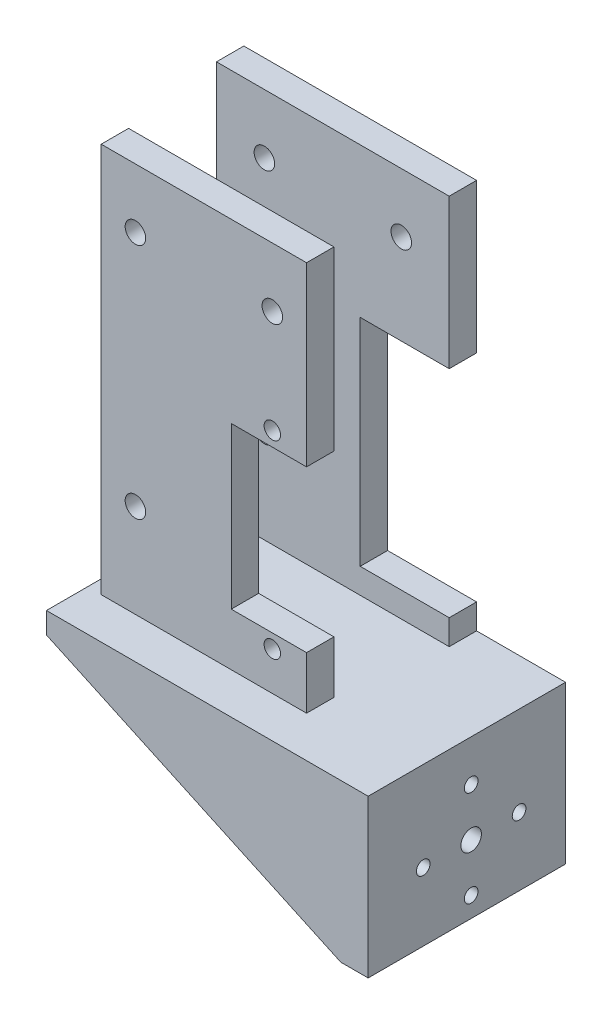
SolidWorks part; units mm, degrees
ref_plane "前视基准面" through (0, 0, 0) normal (0, 0, 1) x (1, 0, 0)
ref_plane "上视基准面" through (0, 0, 0) normal (0, 1, 0) x (1, 0, 0)
ref_plane "右视基准面" through (0, 0, 0) normal (1, 0, 0) x (0, 0, -1)
ref_plane "基准面1" through (30, 0, 0) normal (1, 0, 0) x (0, 0, -1)
sketch "草图1" plane through (0, 0, 0) normal (0, 0, 1) x (1, 0, 0)
  line L0 (0, 19.2229) -> (0, -22.2141) construction
  line L1 (-15, -26) -> (-15, -54)
  line L2 (-15, 26) -> (15, 26)
  line L3 (-15, 26) -> (-15, -26)
  line L6 (-15, 26) -> (15, -26) construction
  line L7 (-15, -26) -> (15, 26) construction
  line L8 (-15, -54) -> (30, -54)
  line L11 (15, 26) -> (15, 0.1667)
  line L12 (15, 0.1667) -> (4, 0.1667)
  line L13 (4, 0.1667) -> (4, -23.3333)
  line L14 (4, -23.3333) -> (15, -23.3333)
  line L15 (15, -23.3333) -> (15, -26)
  line L16 (15, -26) -> (15, -31)
  line L17 (15, -31) -> (30, -31)
  line L18 (30, -31) -> (30, -54)
  circle A0 centre (-10, 17.3333) radius 1.5
  circle A1 centre (10, 17.3333) radius 1.5
  circle A2 centre (-10, -17.3333) radius 1.5
  circle A4 centre (10, 2.2917) radius 1.2
  circle A5 centre (10, -25.3783) radius 1.2
  point P3 (0, 0)
  dimension "D6" = 3
  dimension "D7" = 3
  dimension "D8" = 3
  dimension "D14" = 2.4
  dimension "D15" = 2.4
  dimension "D16" = 6
  dimension "D1" = 30
  dimension "D2" = 52
  dimension "D3" = 10
  dimension "D4" = 10
  dimension "D5" = 10
  dimension "D9" = 28
  dimension "D10" = 45
  dimension "D11" = 17.5
  dimension "D12" = 19.625
  dimension "D13" = 8.045
  dimension "D17" = 10
  dimension "D18" = 10
  dimension "D19" = 6
  dimension "5" = 5
  dimension "D21" = 15
extrude "凸台-拉伸1" add sketch "草图1" along normal blind 4
sketch "草图2" plane through (30, 0, 0) normal (1, 0, 0) x (0, 0, -1)
  line L0 (-4.8995, -34.1005) -> (15, -34.1005)
  line L1 (15, -34.1005) -> (15, -54)
  line L2 (15, -54) -> (-4.8995, -54)
  line L7 (-4, -54) -> (0, -54) construction
  line L8 (-4.8995, -34.1005) -> (-4.8995, -54)
  circle A4 centre (0.1005, -39.1005) radius 1.5
  circle A5 centre (10, -39.1005) radius 1.5
  circle A6 centre (0.1005, -49) radius 1.5
  circle A7 centre (10, -49) radius 1.5
  dimension "D3" = 14
  dimension "D5" = 5
  dimension "D7" = 3
  dimension "D9" = 3
  dimension "D6" = 3
  dimension "D8" = 3
  dimension "D11" = 9.8995
  dimension "D2" = 14
  dimension "D4" = 5
  dimension "D12" = 9.8995
  dimension "D13" = 5
  dimension "D14" = 5
  dimension "D15" = 5
  dimension "D16" = 15
  dimension "D10" = 5
extrude "凸台-拉伸2" add sketch "草图2" against normal blind 4
sketch "草图13" plane through (0, 0, 4.8995) normal (0, 0, 1) x (1, 0, 0)
  line L1 (26, -54) -> (30, -54)
  line L2 (26, -54) -> (26, -34.1005)
  line L3 (26, -34.1005) -> (30, -34.1005)
  line L4 (30, -54) -> (30, -34.1005)
sketch "草图3" plane through (0, 0, 0) normal (0, 0, -1) x (-1, 0, 0)
  line L0 (15, 26) -> (15, -54) construction
  line L1 (-30, -34.1005) -> (15, -34.1005)
  line L2 (-30, -34.1005) -> (-30, -31)
  line L3 (-30, -31) -> (15, -31)
  line L4 (15, -34.1005) -> (15, -31)
  dimension "D1" = 3.1005
extrude "凸台-拉伸3" add sketch "草图3" along normal up to surface (15 mm away) and the other way blind 10 up to face at (28, -44.0503, -15)
sketch "草图4" plane through (-15, 0, 0) normal (-1, 0, 0) x (0, 0, 1)
  line L1 (0, 26) -> (0, -31) construction
  line L3 (0, -26) -> (0, -31)
  line L5 (0, -31) -> (-14.84, -31)
  line L7 (0, -26) -> (-14.84, -26)
  line L8 (-14.84, -31) -> (-14.84, -26)
  dimension "D1" = 5
  dimension "D2" = 14.84
extrude "凸台-拉伸4" add sketch "草图4" against normal blind 16 separate body
extrude "切除-拉伸1" cut sketch "草图4<3>" against normal blind 13
sketch "草图4<3>" plane through (-15, 0, 0) normal (-1, 0, 0) x (0, 0, 1) same geometry as "草图4"
extrude "凸台-拉伸5" add sketch "草图4" against normal blind 6 separate body
extrude "切除-拉伸4" cut sketch "草图4<6>" against normal blind 3
sketch "草图4<6>" plane through (-15, 0, 0) normal (-1, 0, 0) x (0, 0, 1) same geometry as "草图4"
sketch "草图7" plane through (0, 0, 0) normal (0, 0, -1) x (-1, 0, 0)
  line L0 (-26, -34.1005) -> (-26, -37.6039) construction
  line L1 (15, -54) -> (-26, -54)
  line L2 (15, -54) -> (15, -34.1005)
  line L3 (15, -34.1005) -> (-26, -34.1005)
  line L4 (-26, -54) -> (-26, -34.1005)
extrude "切除-拉伸6" cut sketch "草图7" against normal blind 4
sketch "草图10" plane through (0, 0, 10) normal (0, 0, 1) x (1, 0, 0)
  line L0 (26, -54) -> (-15, -34.1005)
  line L1 (-15, -34.1005) -> (26, -34.1005)
  line L2 (26, -34.1005) -> (26, -54)
extrude "凸台-拉伸7" add sketch "草图10" against normal blind 4
sketch "草图12" plane through (30, 0, 0) normal (1, 0, 0) x (0, 0, -1)
  circle A0 centre (5.0503, -44.0503) radius 1.5
  dimension "D1" = 3
extrude "切除-拉伸8" cut sketch "草图12" against normal up to surface (4 mm away) up to face at (26, -39.1005, -0.8003)
extrude "凸台-拉伸8" add sketch "草图13" along normal up to surface (5.1005 mm away) up to face at (13.6667, -36.3836, 10)
sketch "草图14" plane through (30, 0, 0) normal (1, 0, 0) x (0, 0, -1)
  circle A0 centre (0.1005, -49) radius 1.5
  circle A1 centre (0.1005, -39.1005) radius 1.5
extrude "切除-拉伸9" cut sketch "草图14" against normal up to surface (4 mm away) up to face at (26, -44.0503, -3.5503)
sketch "草图15" plane through (0, 0, -15) normal (0, 0, -1) x (-1, 0, 0)
  line L0 (-30, -31) -> (-30, -54)
  line L1 (-30, -54) -> (-26, -54)
  line L2 (-26, -54) -> (-26, -34.1005)
  line L3 (-26, -34.1005) -> (15, -34.1005)
  line L4 (15, -34.1005) -> (15, -31)
  line L5 (15, -31) -> (-30, -31)
extrude "凸台-拉伸9" add sketch "草图15" along normal blind 3.84
sketch "草图16" plane through (0, -31, 0) normal (0, 1, 0) x (1, 0, 0)
  line L1 (17, 18.84) -> (-17, 18.84)
  line L2 (17, 18.84) -> (17, 14.84)
  line L3 (17, 14.84) -> (-17, 14.84)
  line L4 (-17, 18.84) -> (-17, 14.84)
  line L5 (15, -4) -> (15, 0) construction
  line L6 (-15, 0) -> (-15, 18.84) construction
  dimension "D1" = 4
  dimension "D2" = 2
  dimension "D3" = 2
extrude "凸台-拉伸10" add sketch "草图16" along normal up to surface (57 mm away) up to face at (0, 26, 2)
sketch "草图17" plane through (0, 0, 4) normal (0, 0, 1) x (1, 0, 0)
  circle A0 centre (-10, -17.3333) radius 1.5
  circle A1 centre (-10, 17.3333) radius 1.5
  circle A2 centre (10, 17.3333) radius 1.5
  dimension "D1" = 3
  dimension "D2" = 3
  dimension "D3" = 3
extrude "切除-拉伸10" cut sketch "草图17" against normal up to surface (22.84 mm away) up to face at (8.2, -24.8201, -18.84)
sketch "草图18" plane through (0, -31, 0) normal (0, -1, 0) x (1, 0, 0)
  line L1 (-17, -14.84) -> (-15, -14.84)
  line L2 (-17, -14.84) -> (-17, -17.84)
  line L3 (-17, -17.84) -> (-15, -17.84)
  line L4 (-15, -14.84) -> (-15, -17.84)
extrude "凸台-拉伸11" add sketch "草图18" along normal up to surface (3.1005 mm away) up to face at (5.5, -34.1005, -6.42)
sketch "草图19" plane through (-15, 0, 0) normal (-1, 0, 0) x (0, 0, 1)
  line L1 (10, -31) -> (-14.84, -31)
  line L2 (10, -31) -> (10, -34.1005)
  line L3 (10, -34.1005) -> (-14.84, -34.1005)
  line L4 (-14.84, -31) -> (-14.84, -34.1005)
extrude "凸台-拉伸12" add sketch "草图19" along normal up to surface (2 mm away) up to face at (-17, -13.0335, -17.1733)
sketch "草图20" plane through (0, 0, 10) normal (0, 0, 1) x (1, 0, 0)
  line L0 (26, -54) -> (-17, -34.1005)
  line L1 (-17, -34.1005) -> (26, -34.1005)
  line L2 (26, -34.1005) -> (26, -54)
extrude "凸台-拉伸13" add sketch "草图20" against normal up to surface (4 mm away) up to face at (12.3333, -40.7337, 6)
sketch "草图21" plane through (0, 0, -14.84) normal (0, 0, 1) x (1, 0, 0)
  line L0 (17, 26) -> (17, -31) construction
  line L1 (4, 4.1667) -> (17, 4.1667)
  line L2 (4, 4.1667) -> (4, -27.3333)
  line L3 (4, -27.3333) -> (17, -27.3333)
  line L4 (17, 4.1667) -> (17, -27.3333)
  line L6 (4, 0.1667) -> (15, 0.1667) construction
  line L7 (15, -23.3333) -> (4, -23.3333) construction
  dimension "D1" = 4
  dimension "D2" = 4
  dimension "D3" = 13
extrude "切除-拉伸11" cut sketch "草图21" against normal up to surface (4 mm away) up to face at (-8.5, -17.3333, -18.84)
extrude "切除-拉伸12" cut sketch "草图4<7>" against normal up to surface (16 mm away) up to face at (1, -28.5, -7.42)
sketch "草图4<7>" plane through (-15, 0, 0) normal (-1, 0, 0) x (0, 0, 1) same geometry as "草图4"
sketch "草图22" plane through (0, 0, -17.84) normal (0, 0, -1) x (-1, 0, 0)
  line L1 (15, -34.1005) -> (17, -34.1005)
  line L2 (15, -34.1005) -> (15, -31)
  line L3 (15, -31) -> (17, -31)
  line L4 (17, -34.1005) -> (17, -31)
extrude "凸台-拉伸14" add sketch "草图22" along normal blind 1
sketch "草图23" plane through (30, 0, 0) normal (1, 0, 0) x (0, 0, -1)
  circle A0 centre (0.1005, -49) radius 1.5
  circle A1 centre (0.1005, -39.1005) radius 1.5
  circle A2 centre (10, -49) radius 1.5
  circle A3 centre (10, -39.1005) radius 1.5
extrude "凸台-拉伸15" add sketch "草图23" against normal up to surface (4 mm away) up to face at (26, -49, -1.6005)
sketch "草图24" plane through (30, 0, 0) normal (1, 0, 0) x (0, 0, -1)
  circle A0 centre (-1.9497, -44.0503) radius 1
  circle A1 centre (12.0503, -44.0503) radius 1
  circle A2 centre (5.0503, -37.0503) radius 1
  circle A3 centre (5.0503, -51.0503) radius 1
  circle A4 centre (5.0503, -44.0503) radius 1.5 construction
  dimension "D1" = 7
  dimension "D2" = 7
  dimension "D3" = 7
  dimension "D4" = 7
  dimension "D5" = 2
  dimension "D6" = 2
  dimension "D7" = 2
  dimension "D8" = 2
extrude "切除-拉伸13" cut sketch "草图24" against normal up to surface (4 mm away) up to face at (26, -44.0503, -3.5503)
